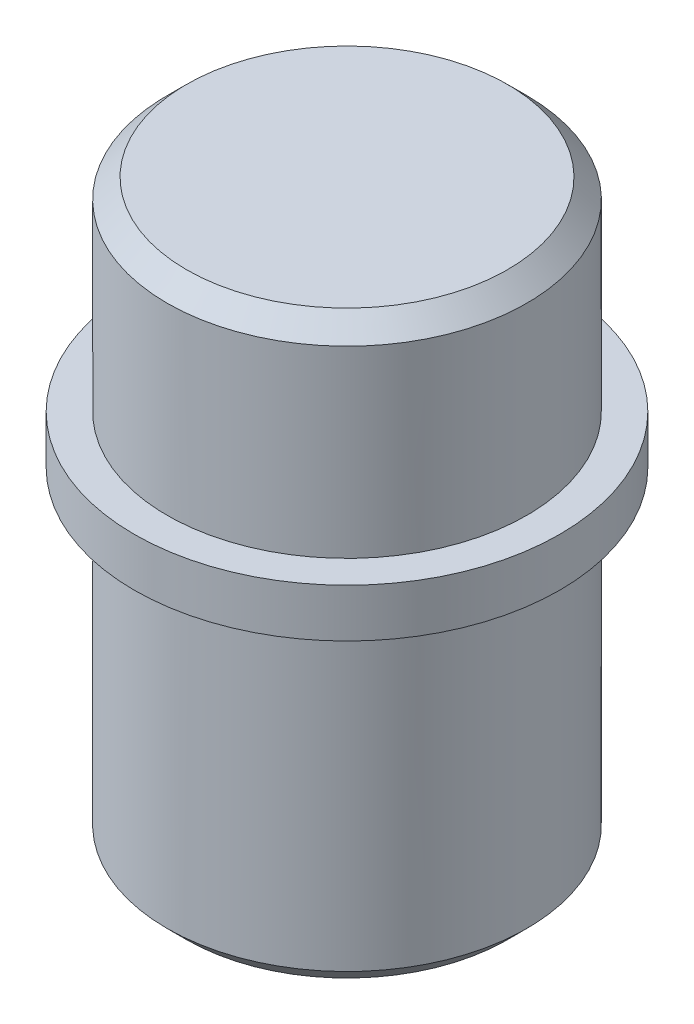
SolidWorks part; units mm, degrees
ref_plane "Front Plane" through (0, 0, 0) normal (0, 0, 1) x (1, 0, 0)
ref_plane "Top Plane" through (0, 0, 0) normal (0, 1, 0) x (1, 0, 0)
ref_plane "Right Plane" through (0, 0, 0) normal (1, 0, 0) x (0, 0, -1)
sketch "Sketch1" plane through (0, 0, 0) normal (0, 1, 0) x (1, 0, 0)
  circle A0 centre (0, 0) radius 9.3
  dimension "D1" = 18.6
extrude "Boss-Extrude1" add sketch "Sketch1" along normal mid plane 30
cosmetic thread "Cosmetic Thread1" parameters "D1"=10.5, "D2"=15.797
chamfer "Chamfer1" distance 1 angle 45 2 edges at (0, -15, 9.3) (0, 15, 9.3)
sketch "Sketch2" plane through (0, -15, 0) normal (0, -1, 0) x (1, 0, 0)
  circle A0 centre (0, 0) radius 11
  dimension "D1" = 22
extrude "Boss-Extrude2" add sketch "Sketch2" against normal blind 2.5 from offset 17 offset against normal yes
